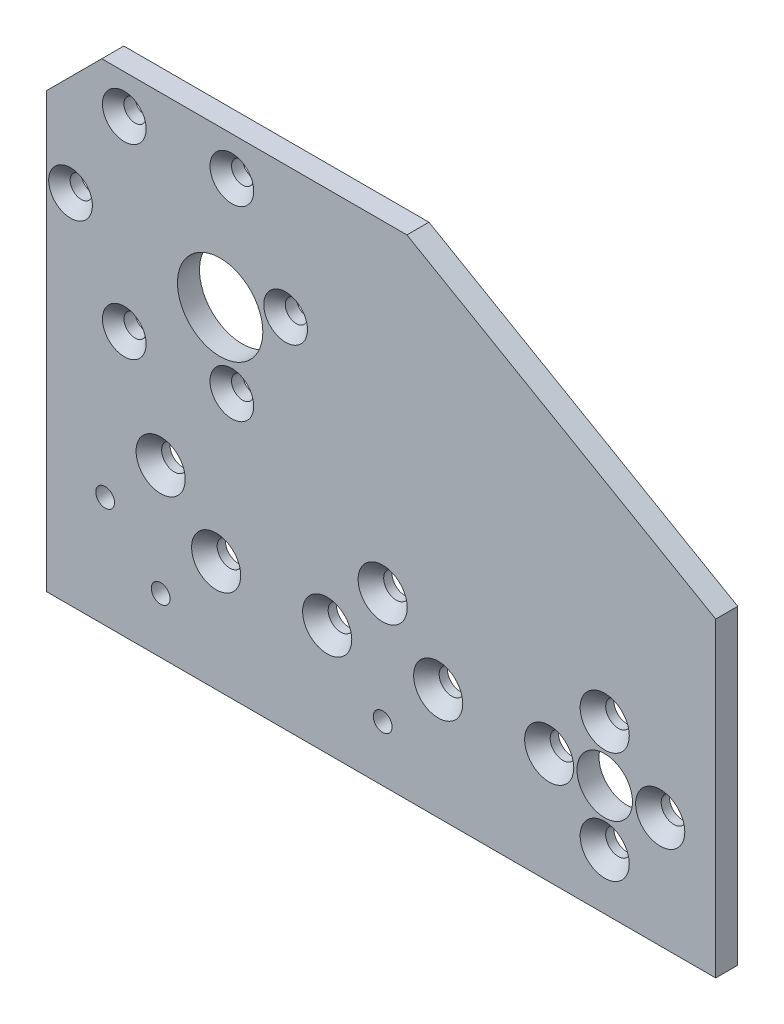
SolidWorks part; units mm, degrees
material "6061-T6 (SS)"
ref_plane "Front" through (0, 0, 0) normal (0, 0, 1) x (1, 0, 0)
ref_plane "Top" through (0, 0, 0) normal (0, 1, 0) x (1, 0, 0)
ref_plane "Right" through (0, 0, 0) normal (1, 0, 0) x (0, 0, -1)
ref_axis "side-side" through (80.9, 0, 0) along (-1, 0, 0)
ref_axis "up-down" through (0, 50, 0) along (0, -1, 0)
ref_axis "front-back" through (0, 0, -80.9) along (0, 0, 1)
sketch "Sketch1" plane through (0, 0, 0) normal (0, 0, 1) x (1, 0, 0)
  line L1 (16, -16) -> (-80.4878, -16)
  line L3 (16, 28.8038) -> (16, -16)
  line L4 (-80.4878, -16) -> (-80.4878, 46.5)
  line L5 (16, 28.8038) -> (-28.5071, 54.5)
  line L6 (-28.5071, 54.5) -> (-72.4878, 54.5)
  line L7 (0, 0) -> (-61.4878, 35.5) construction
  line L8 (-72.4878, 54.5) -> (-80.4878, 46.5)
  circle A1 centre (0, 0) radius 4
  circle A5 centre (-69.2378, 48.9234) radius 1.25 construction
  circle A7 centre (-53.7378, 48.9234) radius 1.25 construction
  circle A9 centre (-76.9878, 35.5) radius 1.25 construction
  circle A11 centre (-69.2378, 22.0766) radius 1.25 construction
  circle A13 centre (-53.7378, 22.0766) radius 1.25 construction
  circle A15 centre (-45.9878, 35.5) radius 1.25 construction
  circle A17 centre (-55.4256, 32) radius 6 construction
  dimension "D1" = 8
  dimension "D2" = 8
extrude "Boss-Extrude1" add sketch "Sketch1" against normal blind 3.175
sketch "Sketch2" plane through (0, 0, 0) normal (0, 0, 1) x (1, 0, 0)
  circle A3 centre (-8, 0) radius 1.3525 construction
  circle A5 centre (0, 8) radius 1.3525 construction
hole_wizard "CSK for M3 Flat Head Machine Screw1" positions "Sketch3" profile "Sketch4" countersink size "M3" standard "ANSI Metric" end condition through all
sketch "Sketch3" plane through (0, 0, 0) normal (0, 0, 1) x (1, 0, 0)
  point P0 (-69.2378, 48.9234)
  point P3 (-53.7378, 48.9234)
  point P6 (-45.9878, 35.5)
  point P9 (-53.7378, 22.0766)
  point P12 (-69.2378, 22.0766)
  point P15 (-76.9878, 35.5)
sketch "Sketch4" plane through (-69.2378, 48.9234, 0) normal (1, 0, 0) x (0, -1, 0)
  line L0 (0, 0) -> (0, 3.175)
  line L1 (0, 3.175) -> (1.6, 3.175)
  line L2 (1.6, 3.175) -> (1.6, 1.55)
  line L3 (1.6, 1.55) -> (3.15, 0)
  line L5 (3.15, 0) -> (0, 0)
  line L6 (-1.6, 1.55) -> (-3.15, 0) construction
  line L11 (0, -6.35) -> (0, 107.95) construction
  dimension "Thru Hole Dia." = 3.2
  dimension "Thru Hole Depth" = 3.175
  dimension "Near C'Sink Dia." = 6.3
  dimension "Near C'Sink Angle" = 90
hole_wizard "31/64 (0.48438) Diameter Hole1" positions "Sketch5" profile "Sketch6" hole size "31/64" standard "ANSI Inch" end condition through all
sketch "Sketch5" plane through (0, 0, 0) normal (0, 0, 1) x (1, 0, 0)
  point P0 (-55.4256, 32)
sketch "Sketch6" plane through (-55.4256, 32, 0) normal (1, 0, 0) x (0, -1, 0)
  line L0 (0, 0) -> (0, 3.175)
  line L1 (0, 3.175) -> (6.1516, 3.175)
  line L2 (6.1516, 3.175) -> (6.1516, 0)
  line L5 (6.1516, 0) -> (0, 0)
  line L11 (0, -6.35) -> (0, 107.95) construction
  dimension "Thru Hole Dia." = 12.3033
  dimension "Thru Hole Depth" = 3.175
hole_wizard "CSK for #6 Flat Head Machine Screw1" positions "Sketch7" profile "Sketch8" countersink size "#6" standard "ANSI Inch" end condition through all
sketch "Sketch7" plane through (0, 0, 0) normal (0, 0, 1) x (1, 0, 0)
  circle A0 centre (0, 0) radius 8 construction
  point P0 (0, 8)
  point P3 (-8, 0)
  point P10 (0, -8)
  point P12 (8, 0)
sketch "Sketch8" plane through (0, 8, 0) normal (1, 0, 0) x (0, -1, 0)
  line L0 (0, 0) -> (0, 3.175)
  line L1 (0, 3.175) -> (1.8288, 3.175)
  line L2 (1.8288, 3.175) -> (1.8288, 1.9723)
  line L3 (1.8288, 1.9723) -> (3.5433, 0)
  line L5 (3.5433, 0) -> (0, 0)
  line L6 (-1.8288, 1.9723) -> (-3.5433, 0) construction
  line L11 (0, -6.35) -> (0, 107.95) construction
  dimension "Thru Hole Dia." = 3.6576
  dimension "Thru Hole Depth" = 3.175
  dimension "Near C'Sink Dia." = 7.0866
  dimension "Near C'Sink Angle" = 82
hole_wizard "#6-32 Tapped Hole1" positions "Sketch9" profile "Sketch11" tap size "#6-32" standard "ANSI Inch" end condition through all
sketch "Sketch9" plane through (0, 0, 0) normal (0, 0, 1) x (1, 0, 0)
  line L0 (-32, 8) -> (0, 8) construction
  circle A0 centre (-32, 0) radius 8 construction
  circle A1 centre (-64, 0) radius 8 construction
  point P10 (-32, -8)
  point P25 (-64, -8)
  point P27 (-72, 0)
  dimension "D1" = 32
  dimension "D2" = 32
sketch "Sketch11" plane through (-72, 0, 0) normal (1, 0, 0) x (0, -1, 0)
  line L0 (0, 0) -> (0, 3.175)
  line L1 (0, 3.175) -> (1.3525, 3.175)
  line L2 (1.3525, 3.175) -> (1.3525, 0)
  line L5 (1.3525, 0) -> (0, 0)
  line L11 (0, -6.35) -> (0, 107.95) construction
  dimension "Thread Major Dia." = 2.7051
  dimension "Thru Tap Drill Depth" = 3.175
hole_wizard "CSK for #6 Flat Head Machine Screw2" positions "Sketch12" profile "Sketch13" countersink size "#6" standard "ANSI Inch" end condition through all
sketch "Sketch12" plane through (0, 0, 0) normal (0, 0, 1) x (1, 0, 0)
  circle A0 centre (-32, 0) radius 8 construction
  circle A1 centre (-64, 0) radius 8 construction
  point P0 (-32, 8)
  point P3 (-24, 0)
  point P7 (-64, 8)
  point P11 (-56, 0)
  point P20 (-40, 0)
sketch "Sketch13" plane through (-32, 8, 0) normal (1, 0, 0) x (0, -1, 0)
  line L0 (0, 0) -> (0, 3.175)
  line L1 (0, 3.175) -> (1.8288, 3.175)
  line L2 (1.8288, 3.175) -> (1.8288, 1.9723)
  line L3 (1.8288, 1.9723) -> (3.5433, 0)
  line L5 (3.5433, 0) -> (0, 0)
  line L6 (-1.8288, 1.9723) -> (-3.5433, 0) construction
  line L11 (0, -6.35) -> (0, 107.95) construction
  dimension "Thru Hole Dia." = 3.6576
  dimension "Thru Hole Depth" = 3.175
  dimension "Near C'Sink Dia." = 7.0866
  dimension "Near C'Sink Angle" = 82
